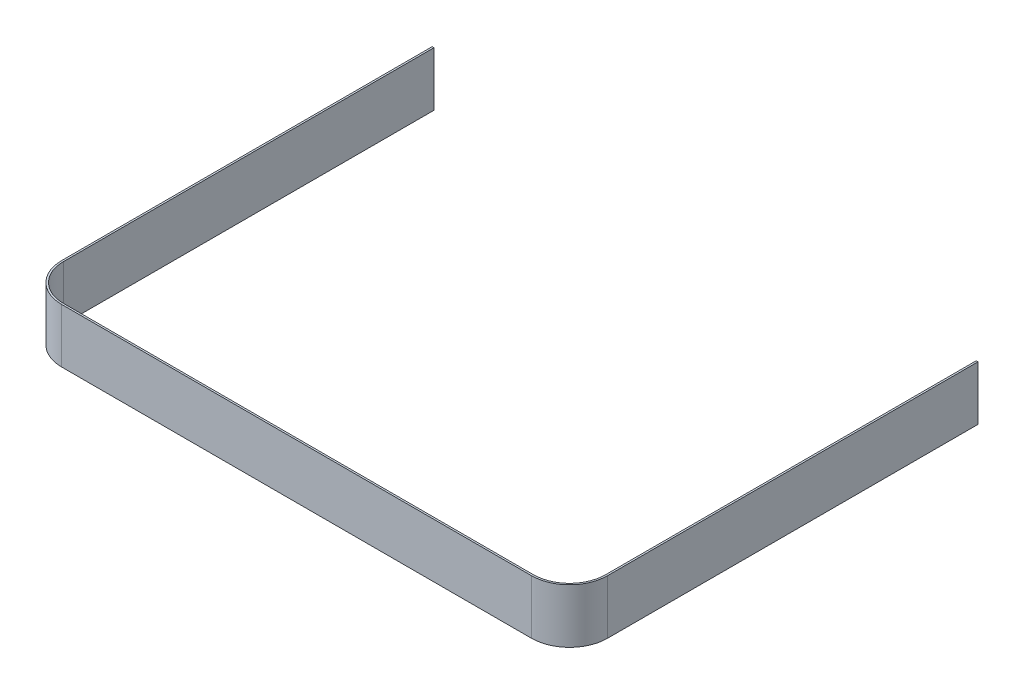
SolidWorks part; units mm, degrees
ref_plane "Ebene vorne" through (0, 0, 0) normal (0, 0, 1) x (1, 0, 0)
ref_plane "Ebene oben" through (0, 0, 0) normal (0, 1, 0) x (1, 0, 0)
ref_plane "Ebene rechts" through (0, 0, 0) normal (1, 0, 0) x (0, 0, -1)
sketch "Skizze1" plane through (0, 0, 0) normal (0, -1, 0) x (1, 0, 0)
  line L0 (0, 75) -> (130, 75)
  line L2 (150, 55) -> (150, -150)
  arc A0 (130, 75) -> (150, 55) centre (130, 55) cw
extrude "Linear-Austragen-Dünn1" add sketch "Skizze1" against normal blind 30 thin thin type one direction reverse wall 1
mirror "Spiegeln1" about plane through (0, 30, 75) normal (1, 0, 0) of "Linear-Austragen-Dünn1"
